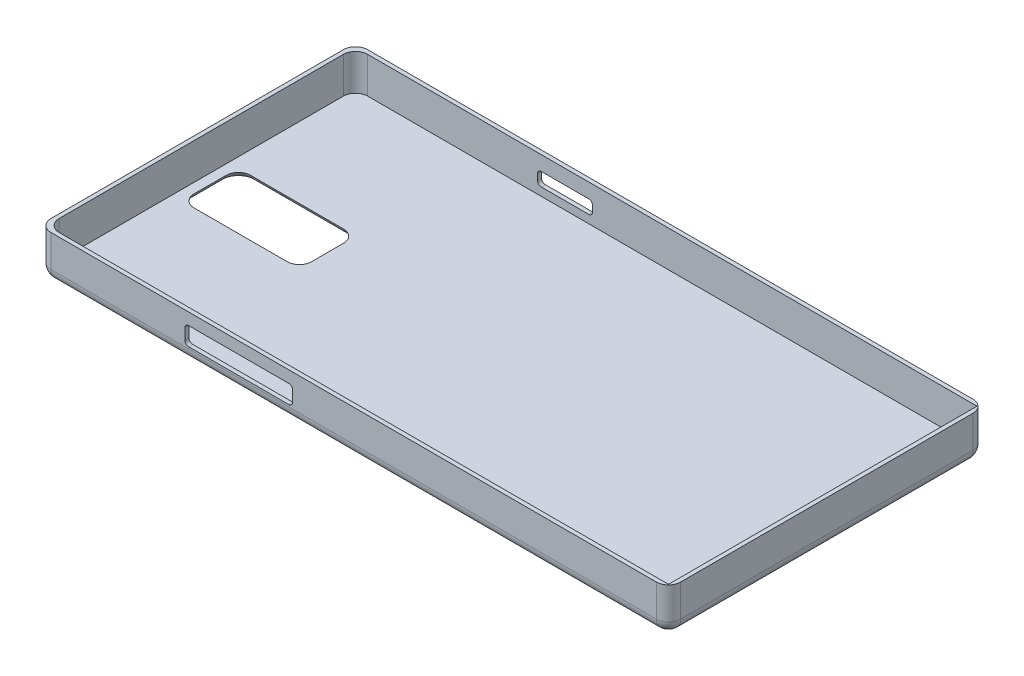
SolidWorks part; units mm, degrees
ref_plane "Front Plane" through (0, 0, 0) normal (0, 0, 1) x (1, 0, 0)
ref_plane "Top Plane" through (0, 0, 0) normal (0, 1, 0) x (1, 0, 0)
ref_plane "Right Plane" through (0, 0, 0) normal (1, 0, 0) x (0, 0, -1)
sketch "Sketch1" plane through (0, 0, 0) normal (0, 1, 0) x (1, 0, 0)
  line L1 (-77.45, -38.95) -> (77.45, -38.95)
  line L2 (-77.45, -38.95) -> (-77.45, 38.95)
  line L3 (-77.45, 38.95) -> (77.45, 38.95)
  line L4 (77.45, -38.95) -> (77.45, 38.95)
  line L5 (-77.45, -38.95) -> (77.45, 38.95) construction
  line L6 (-77.45, 38.95) -> (77.45, -38.95) construction
  point P0 (0, 0)
  dimension "D1" = 154.9
  dimension "D2" = 77.9
extrude "Boss-Extrude1" add sketch "Sketch1" along normal blind 10.9
sketch "Sketch8" plane through (0, 10.9, 0) normal (0, 1, 0) x (1, 0, 0)
  line L1 (-76.45, -37.95) -> (76.45, -37.95)
  line L2 (-76.45, -37.95) -> (-76.45, 37.95)
  line L3 (-76.45, 37.95) -> (76.45, 37.95)
  line L4 (76.45, -37.95) -> (76.45, 37.95)
  line L5 (-76.45, -37.95) -> (76.45, 37.95) construction
  line L6 (-76.45, 37.95) -> (76.45, -37.95) construction
  point P0 (0, 0)
  dimension "D1" = 75.9
  dimension "D2" = 152.9
extrude "Cut-Extrude3" cut sketch "Sketch8" against normal blind 8.9
fillet "Fillet6" radius 2.99 1 edges at (-76.45, 6.45, -37.95)
fillet "Fillet7" radius 2.99 1 edges at (-76.45, 6.45, 37.95)
fillet "Fillet8" radius 2.99 1 edges at (76.45, 6.45, -37.95)
fillet "Fillet9" radius 2.99 1 edges at (76.45, 6.45, 37.95)
fillet "Fillet10" radius 2.99 1 edges at (77.45, 5.45, 38.95)
fillet "Fillet11" radius 2.99 1 edges at (-77.45, 5.45, 38.95)
fillet "Fillet12" radius 2.99 1 edges at (-77.45, 5.45, -38.95)
fillet "Fillet13" radius 2.99 7 edges at (-76.5742, 0, -38.0742) (1.495, 0, -38.95) (77.45, 0, -1.495) (76.5742, 0, 38.0742) (0, 0, 38.95) (-76.5742, 0, 38.0742) (-77.45, 0, 0)
sketch "Sketch12" plane through (0, 2, 0) normal (0, 1, 0) x (1, 0, 0)
  line L1 (-73.9931, -7.2201) -> (-45.0931, -7.2201)
  line L2 (-73.9931, -7.2201) -> (-73.9931, 6.6799)
  line L3 (-73.9931, 6.6799) -> (-45.0931, 6.6799)
  line L4 (-45.0931, -7.2201) -> (-45.0931, 6.6799)
  line L5 (-73.9931, -7.2201) -> (-45.0931, 6.6799) construction
  line L6 (-73.9931, 6.6799) -> (-45.0931, -7.2201) construction
  point P0 (-59.5431, -0.2701)
  dimension "D1" = 28.9
  dimension "D2" = 13.9
extrude "Cut-Extrude4" cut sketch "Sketch12" against normal through all
fillet "Fillet15" radius 2.99 1 edges at (-73.9931, 1, -6.6799)
fillet "Fillet16" radius 2.99 1 edges at (-73.9931, 1, 7.2201)
fillet "Fillet17" radius 2.99 1 edges at (-45.0931, 1, 7.2201)
fillet "Fillet18" radius 2.99 1 edges at (-45.0931, 1, -6.6799)
sketch "Sketch15" plane through (0, 0, 38.95) normal (0, 0, 1) x (1, 0, 0)
  line L1 (-41.5195, 3.4963) -> (-15.0195, 3.4963)
  line L2 (-41.5195, 3.4963) -> (-41.5195, 7.9963)
  line L3 (-41.5195, 7.9963) -> (-15.0195, 7.9963)
  line L4 (-15.0195, 3.4963) -> (-15.0195, 7.9963)
  line L5 (-41.5195, 3.4963) -> (-15.0195, 7.9963) construction
  line L6 (-41.5195, 7.9963) -> (-15.0195, 3.4963) construction
  point P0 (-28.2695, 5.7463)
  dimension "D1" = 26.5
  dimension "D2" = 4.5
extrude "Cut-Extrude8" cut sketch "Sketch15" against normal up to next
sketch "Sketch16" plane through (0, 0, -38.95) normal (0, 0, -1) x (-1, 0, 0)
  line L1 (18.1557, 4.0031) -> (31.6557, 4.0031)
  line L2 (18.1557, 4.0031) -> (18.1557, 7.3031)
  line L3 (18.1557, 7.3031) -> (31.6557, 7.3031)
  line L4 (31.6557, 4.0031) -> (31.6557, 7.3031)
  line L5 (18.1557, 4.0031) -> (31.6557, 7.3031) construction
  line L6 (18.1557, 7.3031) -> (31.6557, 4.0031) construction
  point P0 (24.9057, 5.6531)
  dimension "D1" = 13.5
  dimension "D2" = 3.3
extrude "Cut-Extrude9" cut sketch "Sketch16" against normal up to next
fillet "Fillet19" radius 2.99 8 edges at (-73.1174, 0, 6.3443) (-73.9931, 0, 0.2701) (-73.1174, 0, -5.8042) (-59.5431, 0, -6.6799) (-45.9689, 0, -5.8042) (-45.0931, 0, 0.2701) (-45.9689, 0, 6.3443) (-59.5431, 0, 7.2201)
fillet "Fillet22" radius 0.9 1 edges at (-15.0195, 7.9963, 38.45)
fillet "Fillet23" radius 0.9 1 edges at (-41.5195, 7.9963, 38.45)
fillet "Fillet24" radius 0.9 1 edges at (-15.0195, 3.4963, 38.45)
fillet "Fillet25" radius 0.9 1 edges at (-41.5195, 3.4963, 38.45)
fillet "Fillet29" radius 0.9 4 edges at (-18.1557, 4.0031, -38.45) (-31.6557, 4.0031, -38.45) (-18.1557, 7.3031, -38.45) (-31.6557, 7.3031, -38.45)
fillet "Fillet39" radius 2.99 2 edges at (76.5742, 0.8758, -38.0742) (77.45, 6.945, -38.95)
sketch "Sketch6" plane through (0, 10.9, 0) normal (0, 1, 0) x (1, 0, 0)
  line L1 (-76.45, -37.95) -> (76.45, -37.95)
  line L2 (-76.45, -37.95) -> (-76.45, 37.95)
  line L3 (-76.45, 37.95) -> (76.45, 37.95)
  line L4 (76.45, -37.95) -> (76.45, 37.95)
  line L5 (-76.45, -37.95) -> (76.45, 37.95) construction
  line L6 (-76.45, 37.95) -> (76.45, -37.95) construction
  point P0 (0, 0)
  dimension "D1" = 152.9
  dimension "D2" = 75.9
extrude "Cut-Extrude2" cut sketch "Sketch6" against normal blind 8.9
fillet "Fillet4" radius 2.99 1 edges at (-76.45, 6.45, -37.95)
fillet "Fillet5" radius 2.99 1 edges at (-76.45, 6.45, 37.95)
